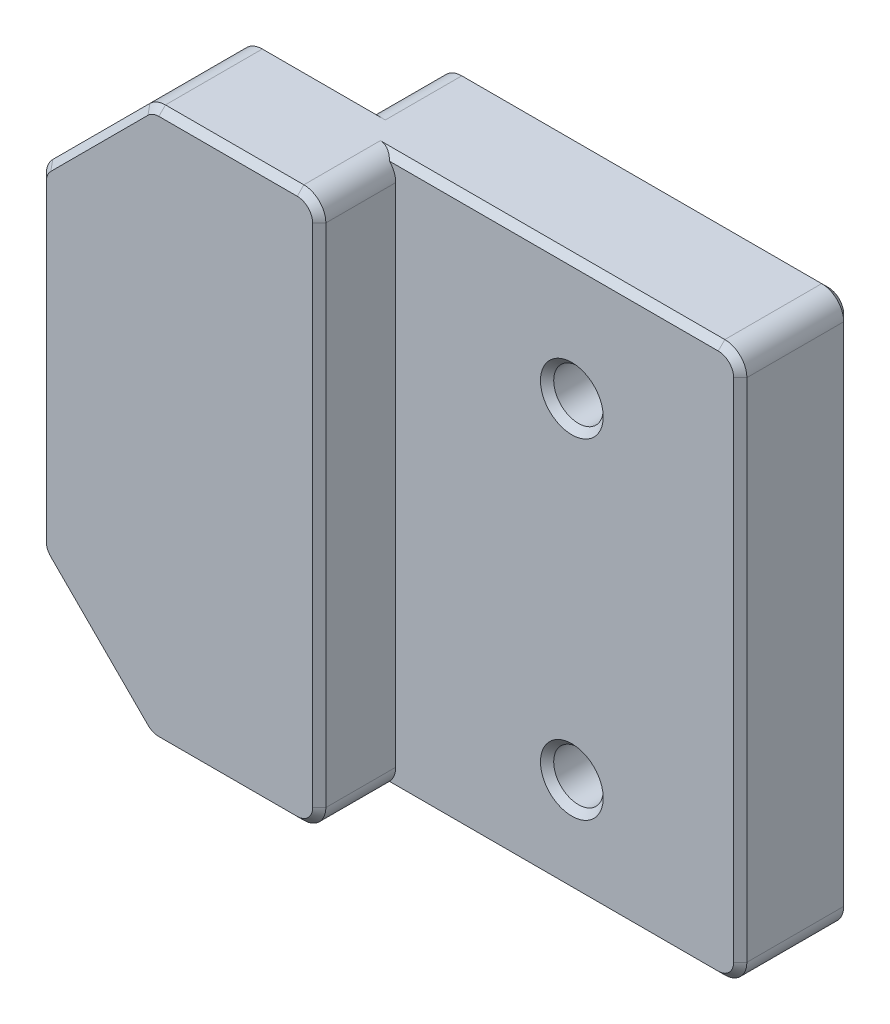
SolidWorks part; units mm, degrees
ref_plane "Front Plane" through (0, 0, 0) normal (0, 0, 1) x (1, 0, 0)
ref_plane "Top Plane" through (0, 0, 0) normal (0, 1, 0) x (1, 0, 0)
ref_plane "Right Plane" through (0, 0, 0) normal (1, 0, 0) x (0, 0, -1)
sketch "Sketch1" plane through (0, 0, 0) normal (0, 1, 0) x (1, 0, 0)
  line L0 (0, 0) -> (-18.35, 0)
  line L1 (-18.35, 0) -> (-18.35, -3.475)
  line L2 (-18.35, -3.475) -> (-28.35, -3.475)
  line L3 (-28.35, -3.475) -> (-28.35, -8.475)
  line L4 (-28.35, -8.475) -> (-15.65, -8.475)
  line L5 (-15.65, -8.475) -> (-15.65, -5)
  line L6 (-15.65, -5) -> (0, -5)
  line L7 (0, -5) -> (0, 0)
  dimension "D1" = 5
  dimension "D2" = 2.7
  dimension "D3" = 18.35
  dimension "D4" = 10
  dimension "D5" = 3.475
  dimension "D6" = 5
extrude "Boss-Extrude1" add sketch "Sketch1" along normal blind 25
sketch "Sketch2" plane through (0, 0, 5) normal (0, 0, 1) x (1, 0, 0)
  line L0 (-7.65, 4.5) -> (-7.65, 19.5) construction
  line L1 (-15.65, 0) -> (0, 0) construction
  line L2 (0, 25) -> (0, 0) construction
  circle A0 centre (-7.65, 4.5) radius 1.125
  circle A1 centre (-7.65, 19.5) radius 1.125
  point P8 (-8, 19.6126)
  dimension "D1" = 2.25
  dimension "D2" = 4.5
  dimension "D3" = 7.65
  dimension "D4" = 15
extrude "Cut-Extrude1" cut sketch "Sketch2" against normal blind 25
chamfer "Chamfer1" distance 5 angle 45 2 edges at (-28.35, 0, 5.975) (-28.35, 25, 5.975)
fillet "Fillet1" radius 1 10 edges at (0, 0, 2.5) (-28.35, 20, 5.975) (-15.65, 25, 6.7375) (-15.65, 0, 6.7375) (-23.35, 0, 5.975) (-28.35, 5, 5.975) (-23.35, 25, 5.975) (0, 25, 2.5) (-18.35, 25, 1.7375) (-18.35, 0, 1.7375)
chamfer "Chamfer2" distance 0.3 angle 45 38 edges at (-6.525, 4.5, 0) (-6.525, 19.5, 0) (-6.525, 4.5, 5) (-6.525, 19.5, 5) (-9.175, 0, 0) (-0.2929, 0.2929, 0) (0, 12.5, 0) (-0.2929, 24.7071, 0) (-9.175, 25, 0) (-28.35, 12.5, 8.475) (-28.2739, 19.9685, 8.475) (-28.2739, 5.0315, 8.475) (-25.85, 22.5, 8.475) (-25.85, 2.5, 8.475) (-23.3185, 24.9239, 8.475) (-23.3185, 0.0761, 8.475) (-19.7929, 25, 8.475) (-19.7929, 0, 8.475) (-15.9429, 24.7071, 8.475) (-15.9429, 0.2929, 8.475) (-15.65, 12.5, 8.475) (-18.0571, 0.2929, 0) (-18.35, 12.5, 0) (-18.0571, 24.7071, 0) (-8.825, 25, 5) (-8.825, 0, 5) (-0.2929, 24.7071, 5) (-0.2929, 0.2929, 5) (0, 12.5, 5) (-20.1429, 0, 3.475) (-23.3185, 0.0761, 3.475) (-25.85, 2.5, 3.475) (-28.2739, 5.0315, 3.475) (-28.35, 12.5, 3.475) (-20.1429, 25, 3.475) (-28.2739, 19.9685, 3.475) (-23.3185, 24.9239, 3.475) (-25.85, 22.5, 3.475)
